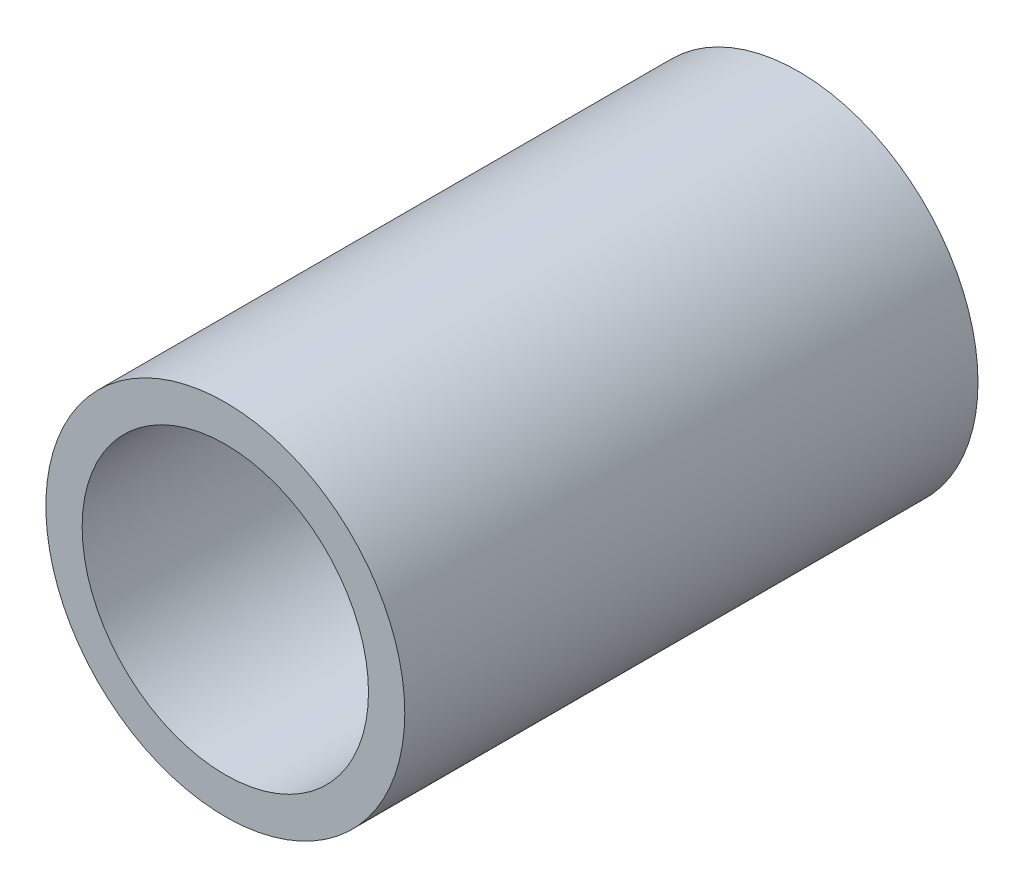
SolidWorks part; units mm, degrees
ref_plane "Front Plane" through (0, 0, 0) normal (0, 0, 1) x (1, 0, 0)
ref_plane "Top Plane" through (0, 0, 0) normal (0, 1, 0) x (1, 0, 0)
ref_plane "Right Plane" through (0, 0, 0) normal (1, 0, 0) x (0, 0, -1)
sketch "Sketch1" plane through (0, 0, 0) normal (0, 0, 1) x (1, 0, 0)
  circle A0 centre (0, 0) radius 16.7005
  dimension "Pipe OD" = 33.401
extrude "Extrude-Thin1" add sketch "Sketch1" along normal mid plane 53.34 thin thin type one direction reverse wall 3.3782
